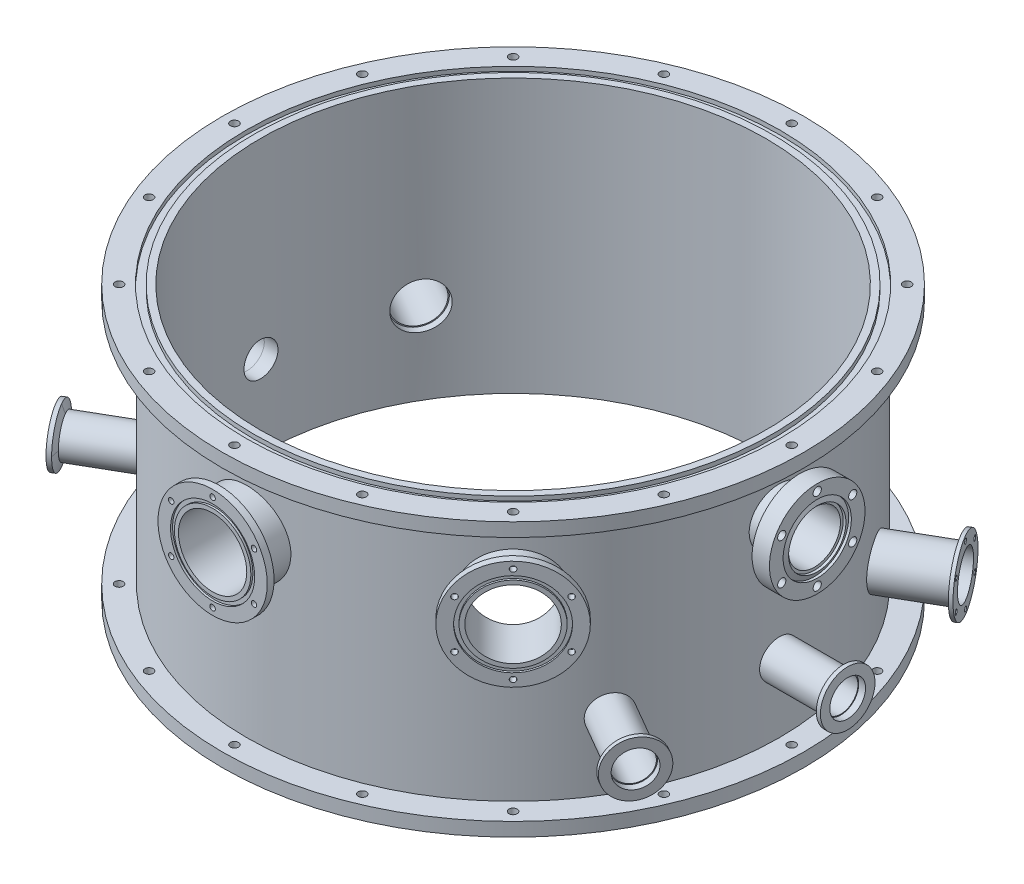
SolidWorks part; units mm, degrees
ref_plane "前视基准面" through (0, 0, 0) normal (0, 0, 1) x (1, 0, 0)
ref_plane "上视基准面" through (0, 0, 0) normal (0, 1, 0) x (1, 0, 0)
ref_plane "右视基准面" through (0, 0, 0) normal (1, 0, 0) x (0, 0, -1)
sketch "草图1" plane through (0, 0, 0) normal (0, 1, 0) x (1, 0, 0)
  circle A0 centre (0, 0) radius 185
  circle A1 centre (0, 0) radius 195
  dimension "D1" = 370
  dimension "D2" = 390
extrude "凸台-拉伸1" add sketch "草图1" along normal blind 200
sketch "草图2" plane through (0, 0, 0) normal (0, -1, 0) x (1, 0, 0)
  circle A0 centre (0, 0) radius 204
  circle A1 centre (0, 0) radius 213
  circle A2 centre (0, 204) radius 3
  circle A3 centre (78.0674, 188.4714) radius 3
  circle A4 centre (144.2498, 144.2498) radius 3
  circle A5 centre (188.4714, 78.0674) radius 3
  circle A6 centre (204, 0) radius 3
  circle A7 centre (188.4714, -78.0674) radius 3
  circle A8 centre (144.2498, -144.2498) radius 3
  circle A9 centre (78.0674, -188.4714) radius 3
  circle A10 centre (0, -204) radius 3
  circle A11 centre (-78.0674, -188.4714) radius 3
  circle A12 centre (-144.2498, -144.2498) radius 3
  circle A13 centre (-188.4714, -78.0674) radius 3
  circle A14 centre (-204, 0) radius 3
  circle A15 centre (-188.4714, 78.0674) radius 3
  circle A16 centre (-144.2498, 144.2498) radius 3
  circle A17 centre (-78.0674, 188.4714) radius 3
  point P39 (0, 0)
  circle M1 centre (0, 0) radius 195
  circle M2 centre (0, 0) radius 185
  dimension "D1" = 408
  dimension "D2" = 426
  dimension "D3" = 6
  dimension "D4" = 16
extrude "凸台-拉伸2" add sketch "草图2" against normal blind 10 contours A1 A17 A0 A2 A3 A4 A5 A6 A7 A8 A9 A10 A11 A12 A13 A14 A15 A16 | A17 A0 A16 A15 A14 A13 A12 A11 A10 A9 A8 A7 A6 A5 A4 A3 A2 M1 | M1 M2
ref_plane "基准面1" through (0, 100, 0) normal (0, 1, 0) x (1, 0, 0)
mirror "镜向1" about plane through (0, 100, 0) normal (0, 1, 0) of "凸台-拉伸2"
sketch "草图5" plane through (0, 0, 0) normal (1, 0, 0) x (0, 0, -1)
  line L0 (0, 0) -> (0, 60)
  circle A0 centre (0, 60) radius 12.45
  dimension "D2" = 24.9
  dimension "D1" = 60
extrude "切除-拉伸2" cut sketch "草图5" along normal blind 300 contours A0
ref_plane "基准面2" through (190, 0, 0) normal (1, 0, 0) x (0, 0, -1)
sketch "草图6" plane through (190, 0, 0) normal (1, 0, 0) x (0, 0, -1)
  circle A0 centre (0, 60) radius 12.5
  circle A1 centre (0, 60) radius 14
  dimension "D1" = 28
  dimension "D2" = 25
extrude "凸台-拉伸3" add sketch "草图6" along normal blind 50
sketch "草图7" plane through (240, 0, 0) normal (1, 0, 0) x (0, 0, -1)
  circle A0 centre (0, 60) radius 13.1
  circle A1 centre (0, 60) radius 20
  dimension "D1" = 26.2
  dimension "D2" = 40
extrude "凸台-拉伸4" add sketch "草图7" along normal blind 5
sketch "草图8" plane through (0, 0, 0) normal (0, 1, 0) x (1, 0, 0)
  line L0 (0, 0) -> (110.98, 0)
  line L1 (0, 0) -> (43.1856, 74.7996)
  line L2 (0, 0) -> (60.8694, -35.1429)
  dimension "D1" = 60
  dimension "D2" = 90
ref_plane "基准面3" through (0, 0, 0) normal (0.866, 0, 0.5) x (0.5, 0, -0.866)
sketch "草图9" plane through (0, 0, 0) normal (0.866, 0, 0.5) x (0.5, 0, -0.866)
  line L0 (0, 0) -> (0, 60)
  circle A0 centre (0, 60) radius 16.75
  dimension "D2" = 33.5
  dimension "D1" = 60
extrude "切除-拉伸3" cut sketch "草图9" against normal blind 300 contours A0
ref_plane "基准面4" through (-164.5448, 0, -95) normal (0.866, 0, 0.5) x (0.5, 0, -0.866)
sketch "草图10" plane through (-164.5448, 0, -95) normal (0.866, 0, 0.5) x (0.5, 0, -0.866)
  circle A0 centre (0, 60) radius 16
  circle A1 centre (0, 60) radius 17.5
  dimension "D1" = 32
  dimension "D2" = 35
extrude "凸台-拉伸5" add sketch "草图10" against normal blind 50
sketch "草图11" plane through (-207.8461, 0, -120) normal (-0.866, 0, -0.5) x (-0.5, 0, 0.866)
  circle A0 centre (0, 60) radius 25
  circle A1 centre (0, 60) radius 21.5
  circle A2 centre (0, 81.5) radius 1.75
  circle A3 centre (18.6195, 70.75) radius 1.75
  circle A4 centre (18.6195, 49.25) radius 1.75
  circle A5 centre (0, 38.5) radius 1.75
  circle A6 centre (-18.6195, 49.25) radius 1.75
  circle A7 centre (-18.6195, 70.75) radius 1.75
  point P18 (0, 60)
  circle M1 centre (0, 60) radius 16
  circle M2 centre (0, 60) radius 17.5
  dimension "D1" = 50
  dimension "D2" = 43
  dimension "D3" = 3.5
  dimension "D4" = 6
extrude "凸台-拉伸6" add sketch "草图11" along normal blind 2.5 contours A0 A7 A1 A2 A3 A4 A5 A6 | A7 A1 A6 A5 A4 A3 A2 M2 | M2 M1
sketch "草图13" plane through (0, 0, 0) normal (0, 0, 1) x (1, 0, 0)
  line L0 (245, 80) -> (242, 80) construction
  line L1 (242, 80) -> (240, 74)
  line L2 (240, 74) -> (240, 80)
  line L3 (240, 80) -> (242, 80)
  dimension "D1" = 3
sweep "切除-扫描1" cut profiles "草图13" path edge at (240, 60, -20)
sketch "草图14" plane through (0, 0, 0) normal (0, 1, 0) x (1, 0, 0)
  line L0 (0, 0) -> (50.6311, -87.6956)
  line L1 (0, 0) -> (117.4007, 0)
  line L2 (0, 0) -> (-64.0511, -36.9799)
  dimension "D1" = 60
  dimension "D2" = 90
ref_plane "基准面5" through (0, 0, 0) normal (-0.866, 0, 0.5) x (0.5, 0, 0.866)
sketch "草图15" plane through (0, 0, 0) normal (-0.866, 0, 0.5) x (0.5, 0, 0.866)
  line L0 (0, 0) -> (0, 60)
  circle A0 centre (0, 60) radius 12.45
  dimension "D2" = 24.9
  dimension "D1" = 60
extrude "切除-拉伸4" cut sketch "草图15" along normal blind 300 contours A0
ref_plane "基准面6" through (-164.5448, 0, 95) normal (-0.866, 0, 0.5) x (0.5, 0, 0.866)
sketch "草图16" plane through (-164.5448, 0, 95) normal (-0.866, 0, 0.5) x (0.5, 0, 0.866)
  circle A0 centre (0, 60) radius 12.5
  circle A1 centre (0, 60) radius 14
  dimension "D1" = 25
  dimension "D2" = 28
extrude "凸台-拉伸7" add sketch "草图16" along normal blind 50
sketch "草图17" plane through (-207.8461, 0, 120) normal (-0.866, 0, 0.5) x (0.5, 0, 0.866)
  circle A0 centre (0, 60) radius 20
  circle A1 centre (0, 60) radius 13.1
  dimension "D1" = 40
  dimension "D2" = 26.2
extrude "凸台-拉伸8" add sketch "草图17" along normal blind 5
sketch "草图18" plane through (-212.1762, 0, 122.5) normal (-0.866, 0, 0.5) x (0.5, 0, 0.866)
  line L0 (0, 80) -> (0, 40)
  circle A0 centre (0, 60) radius 20 construction
ref_plane "基准面7" through (0, 0, 0) normal (-0.5, 0, -0.866) x (0, -1, 0)
sketch "草图19" plane through (0, 0, 0) normal (-0.5, 0, -0.866) x (0, -1, 0)
  line L0 (-80, 245) -> (-80, 242) construction
  line L1 (-80, 245) -> (-80, 240) construction
  line L2 (-80, 242) -> (-74, 240)
  line L3 (-74, 240) -> (-80, 240)
  line L4 (-80, 240) -> (-80, 242)
  dimension "D1" = 3
sweep "切除-扫描2" cut profiles "草图19" path edge at (-200.8461, 60, 132.1244)
sketch "草图20" plane through (0, 0, 0) normal (-0.866, 0, 0.5) x (0.5, 0, 0.866)
  line L0 (0, 0) -> (0, 60)
  circle A0 centre (0, 60) radius 16
  dimension "D2" = 32
  dimension "D1" = 60
extrude "切除-拉伸5" cut sketch "草图20" against normal blind 300 contours A0
ref_plane "基准面8" through (164.5448, 0, -95) normal (-0.866, 0, 0.5) x (0.5, 0, 0.866)
sketch "草图21" plane through (164.5448, 0, -95) normal (-0.866, 0, 0.5) x (0.5, 0, 0.866)
  circle A0 centre (0, 60) radius 16
  circle A1 centre (0, 60) radius 17.5
  dimension "D1" = 32
  dimension "D2" = 35
extrude "凸台-拉伸9" add sketch "草图21" against normal blind 50
sketch "草图22" plane through (207.8461, 0, -120) normal (0.866, 0, -0.5) x (-0.5, 0, -0.866)
  circle A0 centre (0, 60) radius 16
  circle A1 centre (0, 60) radius 25
  dimension "D1" = 32
  dimension "D2" = 50
extrude "凸台-拉伸10" add sketch "草图22" along normal blind 2.5
sketch "草图23" plane through (0, 0, 0) normal (1, 0, 0) x (0, 0, -1)
  line L0 (0, 0) -> (0, 60)
  circle A0 centre (0, 60) radius 12.45
  dimension "D2" = 24.9
  dimension "D1" = 60
extrude "切除-拉伸6" cut sketch "草图23" against normal blind 300 contours A0
ref_plane "基准面9" through (-190, 0, 0) normal (1, 0, 0) x (0, 0, -1)
sketch "草图24" plane through (-190, 0, 0) normal (1, 0, 0) x (0, 0, -1)
  circle A0 centre (0, 60) radius 12.5
  circle A1 centre (0, 60) radius 14
  dimension "D1" = 25
  dimension "D2" = 28
extrude "凸台-拉伸11" add sketch "草图24" against normal blind 50
sketch "草图25" plane through (-240, 0, 0) normal (-1, 0, 0) x (0, 0, 1)
  circle A0 centre (0, 60) radius 20
  circle A1 centre (0, 60) radius 13.1
  dimension "D1" = 26.2
  dimension "D2" = 40
extrude "凸台-拉伸12" add sketch "草图25" along normal blind 5
sketch "草图26" plane through (0, 0, 0) normal (0, 0, 1) x (1, 0, 0)
  line L0 (-240, 74) -> (-240, 80)
  line L1 (-240, 80) -> (-242, 80)
  line L2 (-240, 80) -> (-245, 80) construction
  line L3 (-242, 80) -> (-240, 74)
  dimension "D1" = 2
sweep "切除-扫描3" cut profiles "草图26" path edge at (-240, 60, 14)
sketch "草图27" plane through (0, 0, 0) normal (0.866, 0, 0.5) x (0.5, 0, -0.866)
  line L0 (0, 0) -> (0, 60)
  circle A0 centre (0, 60) radius 12.45
  dimension "D2" = 24.9
  dimension "D1" = 60
extrude "切除-拉伸7" cut sketch "草图27" along normal blind 300 contours A0
ref_plane "基准面10" through (164.5448, 0, 95) normal (0.866, 0, 0.5) x (0.5, 0, -0.866)
sketch "草图28" plane through (164.5448, 0, 95) normal (0.866, 0, 0.5) x (0.5, 0, -0.866)
  circle A0 centre (0, 60) radius 12.5
  circle A1 centre (0, 60) radius 14
  dimension "D1" = 25
  dimension "D2" = 28
extrude "凸台-拉伸13" add sketch "草图28" along normal blind 50
sketch "草图29" plane through (207.8461, 0, 120) normal (0.866, 0, 0.5) x (0.5, 0, -0.866)
  circle A0 centre (0, 60) radius 13.1
  circle A1 centre (0, 60) radius 20
  dimension "D1" = 26.2
  dimension "D2" = 40
extrude "凸台-拉伸14" add sketch "草图29" along normal blind 5
sketch "草图30" plane through (212.1762, 0, 122.5) normal (0.866, 0, 0.5) x (0.5, 0, -0.866)
  line L0 (0, 80) -> (0, 40)
  circle A0 centre (0, 60) radius 20 construction
ref_plane "基准面11" through (0, 0, 0) normal (-0.5, 0, 0.866) x (0, -1, 0)
sketch "草图31" plane through (0, 0, 0) normal (-0.5, 0, 0.866) x (0, -1, 0)
  line L0 (-74, 240) -> (-80, 240)
  line L1 (-80, 240) -> (-80, 242)
  line L2 (-80, 242) -> (-74, 240)
  dimension "D1" = 2
sweep "切除-扫描4" cut profiles "草图31" path edge at (214.8461, 60, 107.8756)
sketch "草图32" plane through (0, 0, 0) normal (0, 0, 1) x (1, 0, 0)
  line L0 (0, 200) -> (0, 140)
  line L1 (213, 200) -> (-213, 200) construction
  circle A0 centre (0, 140) radius 25
  dimension "D2" = 50
  dimension "D1" = 60
extrude "切除-拉伸8" cut sketch "草图32" along normal blind 300 contours A0
ref_plane "基准面12" through (0, 0, 190) normal (0, 0, 1) x (1, 0, 0)
sketch "草图33" plane through (0, 0, 190) normal (0, 0, 1) x (1, 0, 0)
  circle A0 centre (0, 140) radius 25
  circle A1 centre (0, 140) radius 30
  dimension "D1" = 60
extrude "凸台-拉伸15" add sketch "草图33" along normal blind 25
sketch "草图34" plane through (0, 0, 215) normal (0, 0, 1) x (1, 0, 0)
  circle A0 centre (0, 140) radius 40
  circle A1 centre (0, 140) radius 35
  circle A2 centre (0, 175) radius 2
  circle A3 centre (30.3109, 157.5) radius 2
  circle A4 centre (30.3109, 122.5) radius 2
  circle A5 centre (0, 105) radius 2
  circle A6 centre (-30.3109, 122.5) radius 2
  circle A7 centre (-30.3109, 157.5) radius 2
  point P19 (0, 140)
  circle M1 centre (0, 140) radius 30
  circle M2 centre (0, 140) radius 25
  dimension "D1" = 80
  dimension "D2" = 70
  dimension "D3" = 4
  dimension "D4" = 6
extrude "凸台-拉伸16" add sketch "草图34" along normal blind 5 contours A0 A7 A1 A2 A3 A4 A5 A6 | A7 A1 A6 A5 A4 A3 A2 M1 | M1 M2
sketch "草图35" plane through (0, 0, 220) normal (0, 0, 1) x (1, 0, 0)
  circle A0 centre (0, 140) radius 28
  circle A1 centre (0, 140) radius 30.8
  dimension "D1" = 56
  dimension "D2" = 61.6
extrude "切除-拉伸9" cut sketch "草图35" against normal blind 1.5
sketch "草图36" plane through (0, 0, 0) normal (1, 0, 0) x (0, 0, -1)
  line L0 (0, 200) -> (0, 150)
  line L1 (213, 200) -> (-213, 200) construction
  circle A0 centre (0, 150) radius 19
  dimension "D2" = 38
  dimension "D1" = 50
extrude "切除-拉伸10" cut sketch "草图36" along normal blind 300 contours A0
sketch "草图37" plane through (190, 0, 0) normal (1, 0, 0) x (0, 0, -1)
  circle A0 centre (0, 150) radius 19
  circle A1 centre (0, 150) radius 21
  dimension "D1" = 42
  dimension "D2" = 38
extrude "凸台-拉伸17" add sketch "草图37" along normal blind 20
sketch "草图38" plane through (210, 0, 0) normal (1, 0, 0) x (0, 0, -1)
  circle A0 centre (0, 150) radius 30
  circle A1 centre (0, 150) radius 35
  circle A2 centre (0, 180) radius 3
  circle A3 centre (25.9808, 165) radius 3
  circle A4 centre (25.9808, 135) radius 3
  circle A5 centre (0, 120) radius 3
  circle A6 centre (-25.9808, 135) radius 3
  circle A7 centre (-25.9808, 165) radius 3
  point P19 (0, 150)
  circle M1 centre (0, 150) radius 21
  circle M2 centre (0, 150) radius 19
  dimension "D1" = 60
  dimension "D2" = 70
  dimension "D3" = 6
  dimension "D4" = 6
extrude "凸台-拉伸18" add sketch "草图38" along normal blind 12.7 contours A1 A7 A0 A2 A3 A4 A5 A6 | A7 A0 A6 A5 A4 A3 A2 M1 | M1 M2
sketch "草图39" plane through (222.7, 0, 0) normal (1, 0, 0) x (0, 0, -1)
  circle A0 centre (0, 150) radius 21
  dimension "D1" = 42
extrude "切除-拉伸11" cut sketch "草图39" against normal blind 2
sketch "草图40" plane through (0, 0, 0) normal (0, 0, 1) x (1, 0, 0)
  line L0 (222.7, 150) -> (222.7, 125) construction
  line L1 (222.7, 115) -> (222.7, 185) construction
  line L2 (222.7, 150) -> (201.3167, 150)
  line L3 (222.7, 125) -> (220.7, 125)
  line L4 (220.7, 125) -> (222.7, 129)
  line L5 (222.7, 129) -> (222.7, 125)
  dimension "D1" = 25
  dimension "D2" = 2
  dimension "D3" = 4
revolve "切除-旋转1" cut sketch "草图40" angle 360 about L2
sketch "草图41" plane through (210.0112, 0, -121.25) normal (0.866, 0, -0.5) x (-0.5, 0, -0.866)
  circle A0 centre (0, 60) radius 21.5
  circle A1 centre (0, 81.5) radius 1.75
  circle A2 centre (18.6195, 70.75) radius 1.75
  circle A3 centre (18.6195, 49.25) radius 1.75
  circle A4 centre (0, 38.5) radius 1.75
  circle A5 centre (-18.6195, 49.25) radius 1.75
  circle A6 centre (-18.6195, 70.75) radius 1.75
  point P18 (0, 60)
  dimension "D1" = 43
  dimension "D2" = 3.5
  dimension "D3" = 6
extrude "切除-拉伸12" cut sketch "草图41" against normal blind 2 contours A1 | A6 | A5 | A4 | A3 | A2
sketch "草图42" plane through (0, 0, 0) normal (0, -1, 0) x (1, 0, 0)
  circle A0 centre (0, 0) radius 190
  circle A1 centre (0, 0) radius 195.5
  dimension "D1" = 380
  dimension "D2" = 391
extrude "切除-拉伸13" cut sketch "草图42" against normal blind 3.1
mirror "镜向3" about plane through (0, 100, 0) normal (0, 1, 0) of "切除-拉伸13"
sketch "草图43" plane through (0, 0, 0) normal (0, 1, 0) x (1, 0, 0)
  line L0 (95.1871, -95.1871) -> (0, 0)
  line L1 (0, 0) -> (130.7487, 0)
  line L2 (0, 0) -> (-71.5648, -71.5648)
  dimension "D1" = 45
  dimension "D2" = 90
ref_plane "基准面13" through (0, 0, 0) normal (-0.7071, 0, -0.7071) x (-0.7071, 0, 0.7071)
sketch "草图44" plane through (0, 0, 0) normal (-0.7071, 0, -0.7071) x (-0.7071, 0, 0.7071)
  line L0 (0, 200) -> (0, 140)
  line L1 (3, 200) -> (-3, 200) construction
  circle A0 centre (0, 140) radius 25
  dimension "D2" = 50
  dimension "D1" = 60
extrude "切除-拉伸14" cut sketch "草图44" against normal blind 300 contours A0
ref_plane "基准面14" through (134.3503, 0, 134.3503) normal (-0.7071, 0, -0.7071) x (-0.7071, 0, 0.7071)
sketch "草图45" plane through (134.3503, 0, 134.3503) normal (-0.7071, 0, -0.7071) x (-0.7071, 0, 0.7071)
  circle A0 centre (0, 140) radius 30
  circle A1 centre (0, 140) radius 25
  dimension "D1" = 60
  dimension "D2" = 50
extrude "凸台-拉伸19" add sketch "草图45" against normal blind 25 contours A0 A1
sketch "草图46" plane through (152.028, 0, 152.028) normal (0.7071, 0, 0.7071) x (0.7071, 0, -0.7071)
  circle A0 centre (0, 140) radius 35
  circle A1 centre (0, 140) radius 40
  circle A2 centre (0, 175) radius 2
  circle A3 centre (30.3109, 157.5) radius 2
  circle A4 centre (30.3109, 122.5) radius 2
  circle A5 centre (0, 105) radius 2
  circle A6 centre (-30.3109, 122.5) radius 2
  circle A7 centre (-30.3109, 157.5) radius 2
  point P18 (0, 140)
  circle M1 centre (0, 140) radius 25
  circle M2 centre (0, 140) radius 30
  dimension "D1" = 70
  dimension "D2" = 80
  dimension "D3" = 4
  dimension "D4" = 6
extrude "凸台-拉伸20" add sketch "草图46" along normal blind 5 contours A1 A7 A0 A2 A3 A4 A5 A6 | A7 A0 A6 A5 A4 A3 A2 M2 | M2 M1
sketch "草图47" plane through (155.5635, 0, 155.5635) normal (0.7071, 0, 0.7071) x (0.7071, 0, -0.7071)
  circle A0 centre (0, 140) radius 28
  circle A1 centre (0, 140) radius 30.8
  dimension "D1" = 56
  dimension "D2" = 61.6
extrude "切除-拉伸15" cut sketch "草图47" against normal blind 1.5
